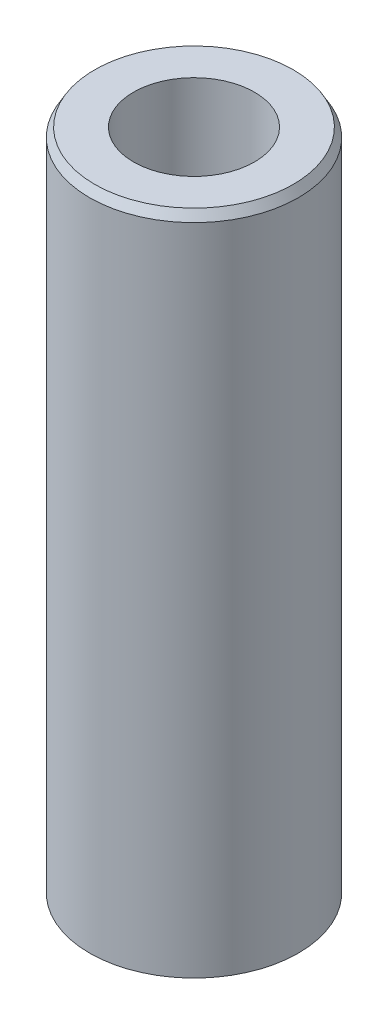
SolidWorks part; units mm, degrees
ref_plane "Front Plane" through (0, 0, 0) normal (0, 0, 1) x (1, 0, 0)
ref_plane "Top Plane" through (0, 0, 0) normal (0, 1, 0) x (1, 0, 0)
ref_plane "Right Plane" through (0, 0, 0) normal (1, 0, 0) x (0, 0, -1)
sketch "Sketch1" plane through (0, 0, 0) normal (0, 1, 0) x (1, 0, 0)
  circle A0 centre (0, 0) radius 20
  dimension "SHAFT_OD" = 40
extrude "Boss-Extrude1" add sketch "Sketch1" along normal blind 127.9528
sketch "Sketch2" plane through (0, 0, 0) normal (0, 1, 0) x (1, 0, 0)
  circle A0 centre (0, 0) radius 11.5852
  dimension "BORE_D" = 23.1704
extrude "Cut-Extrude1" cut sketch "Sketch2" along normal through all
chamfer "Chamfer1" distance 1.7093 angle 30 2 edges at (0, 127.9528, 20) (0, 0, 20) first distance on face at (0, 127.9528, 20) first distance on face at (0, 0, 11.5852)
